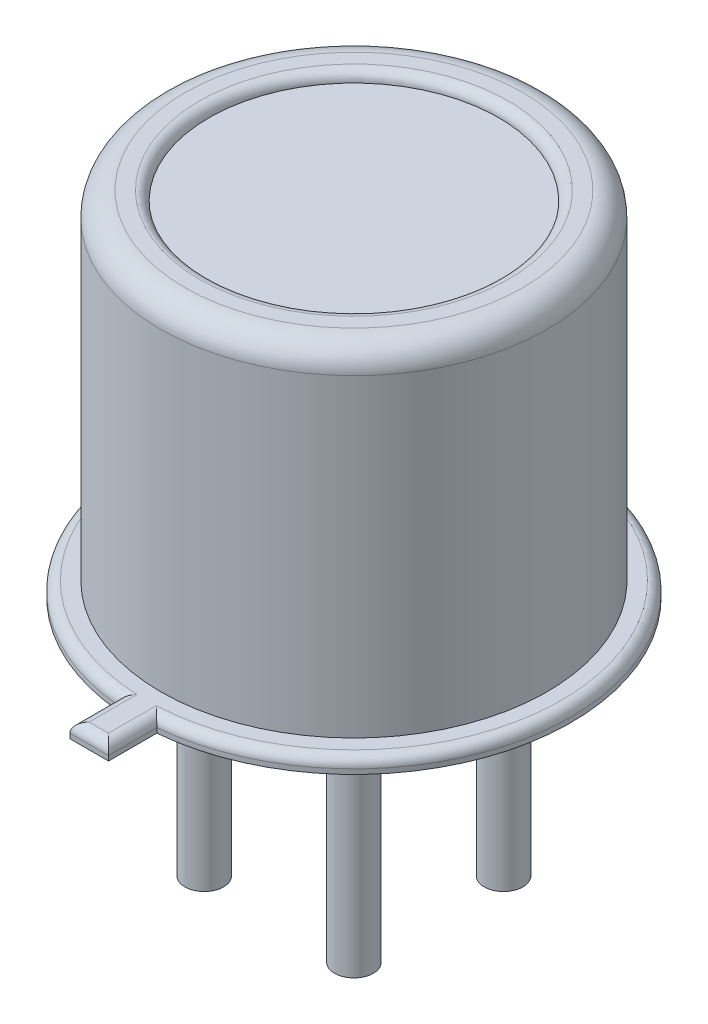
SolidWorks part; units mm, degrees
ref_plane "Спереди" through (0, 0, 0) normal (0, 0, 1) x (1, 0, 0)
ref_plane "Сверху" through (0, 0, 0) normal (0, 1, 0) x (1, 0, 0)
ref_plane "Справа" through (0, 0, 0) normal (1, 0, 0) x (0, 0, -1)
sketch "Sketch1" plane through (0, 0, 0) normal (0, 1, 0) x (1, 0, 0)
  circle A0 centre (0, 0) radius 4
  dimension "D1" = 8
extrude "Boss-Extrude1" add sketch "Sketch1" along normal blind 7
sketch "Sketch2" plane through (0, 0, 0) normal (0, -1, 0) x (1, 0, 0)
  line L1 (0, 5.4824) -> (-0.4, 5.4824)
  line L2 (-0.4, 5.4824) -> (-0.4, 4.4824)
  line L3 (0, 5.4824) -> (0.4, 5.4824)
  line L4 (0.4, 5.4824) -> (0.4, 4.4824)
  arc A1 (-0.4, 4.4824) -> (0.4, 4.4824) centre (0, 0) ccw
  dimension "D2" = 0.4
  dimension "D3" = 0.4
  dimension "D4" = 1
extrude "Boss-Extrude2" add sketch "Sketch2" along normal blind 0.3
sketch "Sketch3" plane through (0, -0.3, 0) normal (0, -1, 0) x (1, 0, 0)
  circle A0 centre (-1.55, 1.55) radius 0.4
  circle A1 centre (1.55, 1.55) radius 0.4
  circle A2 centre (1.55, -1.55) radius 0.4
  circle A3 centre (-1.55, -1.55) radius 0.4
  dimension "D3" = 0.8
  dimension "D1" = 1.55
  dimension "D2" = 1.55
  dimension "D4" = 2
  dimension "D5" = 2
extrude "Boss-Extrude3" add sketch "Sketch3" along normal blind 5
sketch "Sketch4" plane through (0, 7, 0) normal (0, 1, 0) x (1, 0, 0)
  circle A0 centre (0, 0) radius 3
  dimension "D1" = 6
extrude "Cut-Extrude1" cut sketch "Sketch4" against normal blind 0.2
fillet "Fillet1" radius 0.5 1 edges at (0, 7, 4)
fillet "Fillet2" radius 0.2 1 edges at (0, 7, 3)
fillet "Fillet3" radius 0.2 1 edges at (0, 0, -4.5002)
fillet "Fillet4" radius 0.2 3 edges at (0.4, 0, 4.8819) (0, 0, 5.4824) (-0.4, 0, 4.8819)
